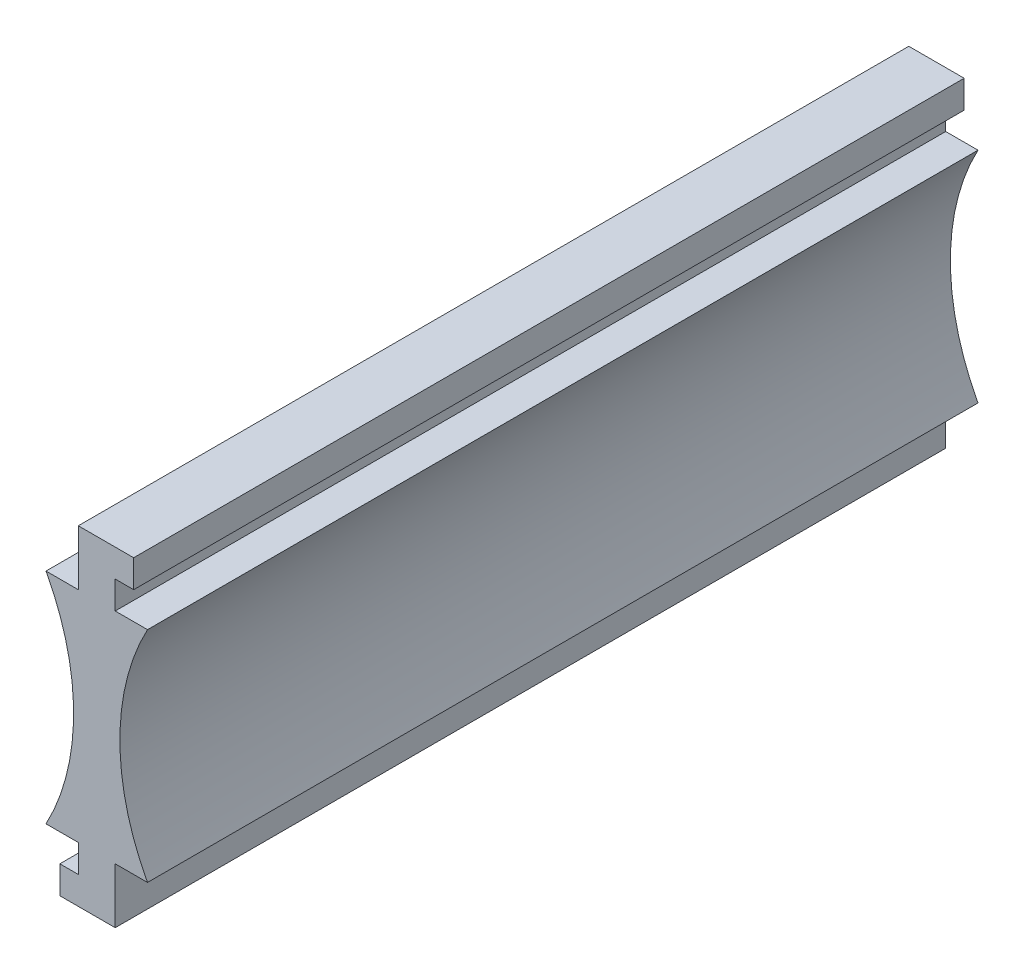
SolidWorks part; units mm, degrees
ref_plane "Спереди" through (0, 0, 0) normal (0, 0, 1) x (1, 0, 0)
ref_plane "Сверху" through (0, 0, 0) normal (0, 1, 0) x (1, 0, 0)
ref_plane "Справа" through (0, 0, 0) normal (1, 0, 0) x (0, 0, -1)
sketch "Эскиз1" plane through (0, 0, 0) normal (0, 0, 1) x (1, 0, 0)
  line L0 (-35.8073, 0) -> (44.0448, 0) construction
  line L28 (0, 75.256) -> (0, -88.7877) construction
  line L29 (-11, -23.725) -> (-4, -23.725)
  line L30 (4, -23.725) -> (11, -23.725)
  line L31 (4, -23.725) -> (4, -35.725)
  line L32 (4, -35.725) -> (-8, -35.725)
  line L33 (-8, -35.725) -> (-8, -29.725)
  line L34 (-8, -29.725) -> (-4, -29.725)
  line L35 (-4, -29.725) -> (-4, -23.725)
  line L36 (-11, 23.725) -> (-4, 23.725)
  line L37 (4, 23.725) -> (11, 23.725)
  line L38 (4, 23.725) -> (4, 29.725)
  line L39 (4, 29.725) -> (8, 29.725)
  line L40 (8, 29.725) -> (8, 35.725)
  line L41 (8, 35.725) -> (-4, 35.725)
  line L42 (-4, 35.725) -> (-4, 23.725)
  arc A4 (11, -23.725) -> (11, 23.725) centre (55.0128, 0) cw
  arc A5 (-11, -23.725) -> (-11, 23.725) centre (-55.0128, 0) ccw
  point P18 (0, 0)
  point P23 (0, 0)
  dimension "D1" = 12
  dimension "D7" = 47.45
  dimension "D9" = 6
  dimension "D6" = 50
  dimension "D2" = 4
  dimension "D3" = 6
  dimension "D4" = 12
  dimension "D5" = 22
  dimension "D8" = 12
  dimension "D10" = 4
  dimension "D11" = 12
  dimension "D12" = 22
extrude "Бобышка-Вытянуть1" add sketch "Эскиз1" against normal blind 180
